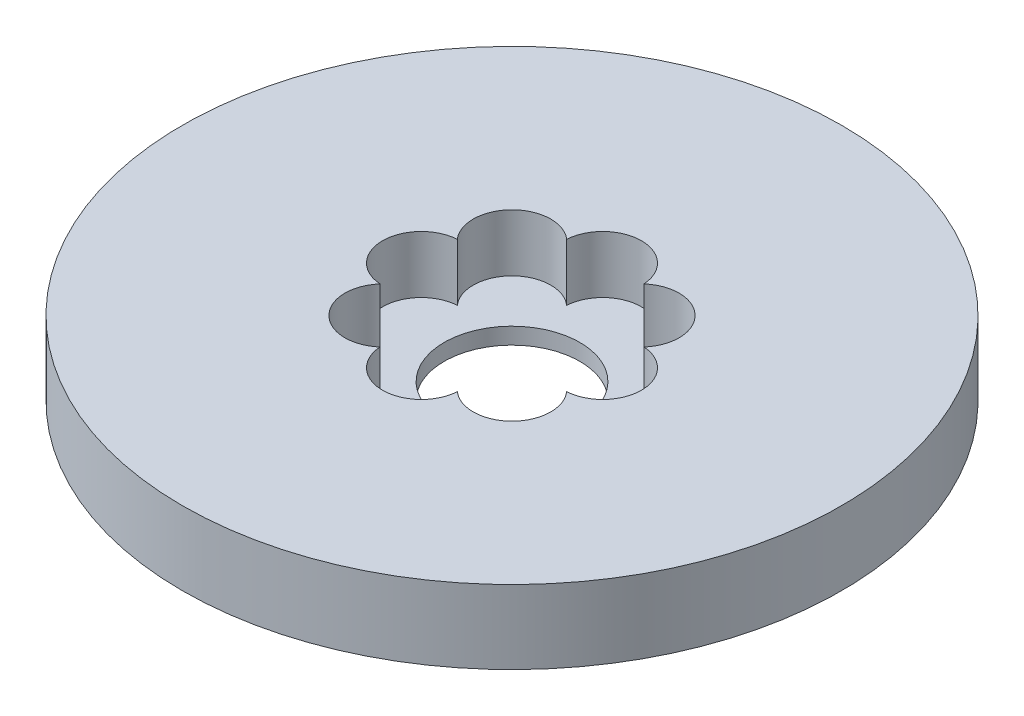
SolidWorks part; units mm, degrees
ref_plane "Front Plane" through (0, 0, 0) normal (0, 0, 1) x (1, 0, 0)
ref_plane "Top Plane" through (0, 0, 0) normal (0, 1, 0) x (1, 0, 0)
ref_plane "Right Plane" through (0, 0, 0) normal (1, 0, 0) x (0, 0, -1)
sketch "Sketch1" plane through (0, 0, 0) normal (0, 1, 0) x (1, 0, 0)
  circle A0 centre (0, 0) radius 85
  dimension "FLANGE_OD" = 170
extrude "Boss-Extrude1" add sketch "Sketch1" along normal blind 19
sketch "Sketch2" plane through (0, 0, 0) normal (0, 1, 0) x (1, 0, 0)
  circle A0 centre (0, 0) radius 17.5
  dimension "BORE_D" = 35
extrude "Cut-Extrude1" cut sketch "Sketch2" along normal through all
sketch "Sketch3" plane through (0, 19, 0) normal (0, 1, 0) x (1, 0, 0)
  circle A0 centre (0, 0) radius 23.3955 construction
  circle A1 centre (-23.3955, 0) radius 10
  dimension "BOLT_D" = 20
  dimension "BOLT_PCD" = 46.7909
extrude "Cut-Extrude2" cut sketch "Sketch3" against normal blind 14.7618
pattern_circular "CirPattern1" count 8 over 360 about axis through (0, 0, 0) along (0, 1, 0) of "Cut-Extrude2"
